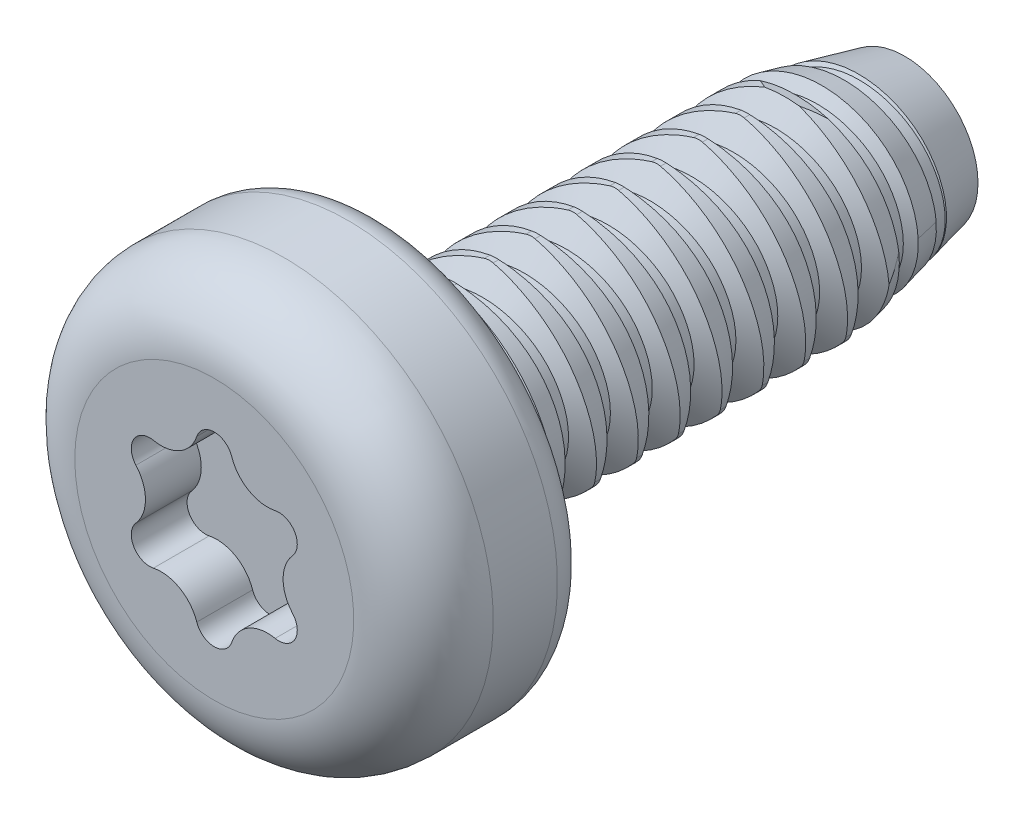
SolidWorks part; units mm, degrees
ref_plane "Front" through (0, 0, 0) normal (0, 0, 1) x (1, 0, 0)
ref_plane "Top" through (0, 0, 0) normal (0, 1, 0) x (1, 0, 0)
ref_plane "Right" through (0, 0, 0) normal (1, 0, 0) x (0, 0, -1)
sketch "Sketch1" plane through (0, 0, 0) normal (0, 0, 1) x (1, 0, 0)
  circle A0 centre (0, 0) radius 2
  dimension "Head Dia" = 4
extrude "Extrude3" add sketch "Sketch1" along normal blind 1.6
ref_plane "Plane1" through (0, 0, 1.6) normal (0, 0, 1) x (1, 0, 0)
sketch "Sketch11" plane through (0, 0, 0) normal (1, 0, 0) x (0, 0, -1)
  line L2 (-1.6, 2) -> (-1.6, -2) construction
  line L4 (0, 2) -> (-1.6, 2) construction
  line L5 (-0.9333, 2) -> (-0.32, 2)
  line L6 (0, -2) -> (0, 2) construction
  line L7 (-1.6, 2) -> (-1.6, 1.3333) construction
  line L8 (-1.6, 0.6667) -> (-1.6, 0) construction
  line L9 (-1.6, 1.3333) -> (-1.6, 0.6667) construction
  line L10 (-1.6, 1.3333) -> (-1.854, 1.3333)
  line L11 (0, 0) -> (-1.6, 0) construction
  line L12 (-1.854, 1.3333) -> (-1.854, 2.254)
  line L13 (-1.854, 2.254) -> (0.254, 2.254)
  line L14 (0.254, 2.254) -> (0.254, 1.68)
  line L15 (0.254, 1.68) -> (0, 1.68)
  arc A0 (-1.6, 1.3333) -> (-0.9333, 2) centre (-0.9333, 1.3333) cw
  arc A1 (-0.32, 2) -> (0, 1.68) centre (-0.32, 1.68) cw
  dimension "D1" = 0.32
  dimension "D2" = 0.254
  dimension "D3" = 0.254
revolve "Cut-Revolve3" cut sketch "Sketch11" angle 360 about L11
sketch "Sketch14" plane through (0, 0, 0) normal (1, 0, 0) x (0, 0, -1)
  line L0 (0.1, 0.7835) -> (0.225, 1) construction
  line L2 (0.225, 1) -> (0.275, 1)
  line L3 (0.275, 1) -> (0.4, 0.7835) construction
  line L4 (0.4, 0.7835) -> (0.1, 0.7835) construction
  line L5 (0.4, 0.7835) -> (0.5, 0.7835) construction
  line L6 (0.1, 0.7835) -> (0, 0.7835) construction
  line L10 (0, 2) -> (0, -2) construction
  line L11 (0.225, 1) -> (0.1, 0.7835)
  line L12 (0.1, 0.7835) -> (0.4, 0.7835)
  line L13 (0.4, 0.7835) -> (0.275, 1)
  line L14 (0, 0) -> (-1.6, 0) construction
  line L15 (0, 0) -> (-1.6, 0) construction
  point P11 (0.25, 1)
  dimension "D1" = 60
  dimension "Pitch" = 0.4
  dimension "D3" = 0.1
  dimension "D4" = 0.05
  dimension "Screw Dia" = 2
ref_plane "Plane2" through (0, 0, -0.25) normal (0, 0, 1) x (1, 0, 0)
sketch "Sketch15" plane through (0, 0, -0.25) normal (0, 0, 1) x (1, 0, 0)
  circle A0 centre (0, 0) radius 1
curve "Helix/Spiral1" pitch 0.4 height 0.6 radius 1 centre (0, 0, -0.25) axis (0, 0, -1) start towards (0, 1, 0)
sketch "Sketch17" plane through (0, 0, 0) normal (1, 0, 0) x (0, 0, -1)
  line L1 (0, 0) -> (5, 0)
  line L2 (0, 0) -> (0, 0.7835)
  line L3 (0, 0.7835) -> (5, 0.7835)
  line L4 (5, 0) -> (5, 0.7835)
  dimension "Body Length" = 5
revolve "Revolve1" add sketch "Sketch17" angle 360 about L11
sweep "Sweep1" add profiles "Sketch14" path "Helix/Spiral1"
pattern_linear "LPattern3" count 12 spacing 0.4 along (0, 0, -1) count 2 spacing 0.4 along (0, 0, 1) of "Sweep1"
sketch "Sketch13" plane through (0, 0, 0) normal (1, 0, 0) x (0, 0, -1)
  line L0 (5, 0.7) -> (3.72, 1)
  line L1 (5, 0.7) -> (5, -0.7) construction
  line L2 (3.72, 1) -> (5, 1)
  line L3 (5, 1) -> (5, 0.7) construction
  line L4 (5, 0.7) -> (5, 0)
  line L5 (0, 0) -> (5, 0) construction
  line L6 (0.225, 1) -> (0.275, 1) construction
  line L7 (7.54, 0) -> (7.54, 1)
  line L8 (7.54, 1) -> (5, 1)
  line L9 (5, 0) -> (7.54, 0)
  dimension "D1" = 13.191
  dimension "D2" = 1.4
  dimension "D3" = 2.54
revolve "Cut-Revolve4" cut sketch "Sketch13" angle 360 about L5
sketch "Sketch12" plane through (0, 0, 1.6) normal (0, 0, 1) x (1, 0, 0)
  line L0 (0, 0) -> (0, 0.8889) construction
  line L1 (0, 0) -> (0.3288, 0.5696) construction
  line L2 (0, 0) -> (-0.3288, 0.5696) construction
  line L3 (-0.3288, 0.5696) -> (0, 0)
  line L4 (0, 0) -> (0.3288, 0.5696)
  arc A0 (-0.3288, 0.5696) -> (-0.1671, 0.7682) centre (-0.5088, 0.8813) ccw
  arc A1 (-0.1671, 0.7682) -> (0.1671, 0.7682) centre (0, 0.7129) cw
  arc A2 (0.1671, 0.7682) -> (0.3288, 0.5696) centre (0.5088, 0.8813) ccw
  circle A5 centre (0, 0) radius 0.8889 construction
  dimension "D1" = 60
  dimension "M" = 1.7778
  dimension "D2" = 0.176
  dimension "D3" = 0.36
extrude "Cut-Extrude1" cut sketch "Sketch12" against normal blind 0.5333
ref_axis "Axis1" through (0, 0, 1.6) along (0, 0, -1)
pattern_circular "CirPattern1" count 6 every 60 about axis through (0, 0, 1.6) along (0, 0, -1) of "Cut-Extrude1"
sketch "Sketch18" plane through (0, 0, -5) normal (0, 0, -1) x (-1, 0, 0)
  line L0 (0, 1) -> (0, 0) construction
  line L1 (0, 0) -> (-0.866, -0.5) construction
  line L2 (0, 0) -> (0.866, -0.5) construction
  circle A0 centre (0, 0) radius 1 construction
  arc A1 (-0.0399, 0.996) -> (0.0399, 0.996) centre (0, 0.8) cw
  arc A2 (-0.8825, -0.4635) -> (-0.8426, -0.5325) centre (-0.6928, -0.4) ccw
  arc A3 (0.8825, -0.4635) -> (0.8426, -0.5325) centre (0.6928, -0.4) cw
  arc A4 (-0.0399, 0.996) -> (-0.8825, -0.4635) centre (0.1844, -0.1064) ccw
  arc A5 (0.0399, 0.996) -> (0.8825, -0.4635) centre (-0.1844, -0.1064) cw
  arc A6 (-0.8426, -0.5325) -> (0.8426, -0.5325) centre (0, 0.2129) ccw
  dimension "D3" = 0.2
  dimension "D4" = 1.125
  dimension "D1" = 120
  dimension "D2" = 120
extrude "Cut-Extrude3" cut sketch "Sketch18" against normal up to surface (5 mm away) flip side to cut up to face at (-1.68, 0, 0)
combine bodies "Combine1" operation type add bodies to combine 148 143
sketch "Sketch19" plane through (0, 0, 0) normal (1, 0, 0) x (0, 0, -1)
  line L0 (5, 1) -> (5, -1) construction
  point P0 (-1.6, 1.3333)
  point P1 (0, 1.68)
  point P2 (3.72, -1)
equation "\"D3@LPattern3\"=\"Pitch@Sketch14\""
equation "\"D1@LPattern3\"=(\"Body Length@Sketch17\"/\"Pitch@Sketch14\")-1"
equation "\"D1@Cut-Extrude1\"=\"Head Ht@Extrude3\"/3"
equation "\"D3@Sketch14\" = \"Pitch@Sketch14\"/4"
equation "\"D4@Sketch14\" = \"Pitch@Sketch14\"/8"
equation "\"D4@LPattern3\" = \"D3@LPattern3\""
equation "\"D4@Helix/Spiral1\" = \"Pitch@Sketch14\""
equation "\"D2@Sketch12\" = \"Head Dia@Sketch1\" * .044"
equation "\"D3@Sketch12\" = \"Head Dia@Sketch1\" * .09"
equation "\"D3@Sketch18\" = \"Screw Dia@Sketch14\"*.1"
equation "\"D4@Sketch18\" = \"Screw Dia@Sketch14\"*.5625"
equation "\"D1@Sketch11\" = \"Head Ht@Extrude3\"/5"
equation "\"M@Sketch12\" = \"Head Dia@Sketch1\"/2.25"
equation "\"D2@Sketch13\" = \"Screw Dia@Sketch14\" * .7"
